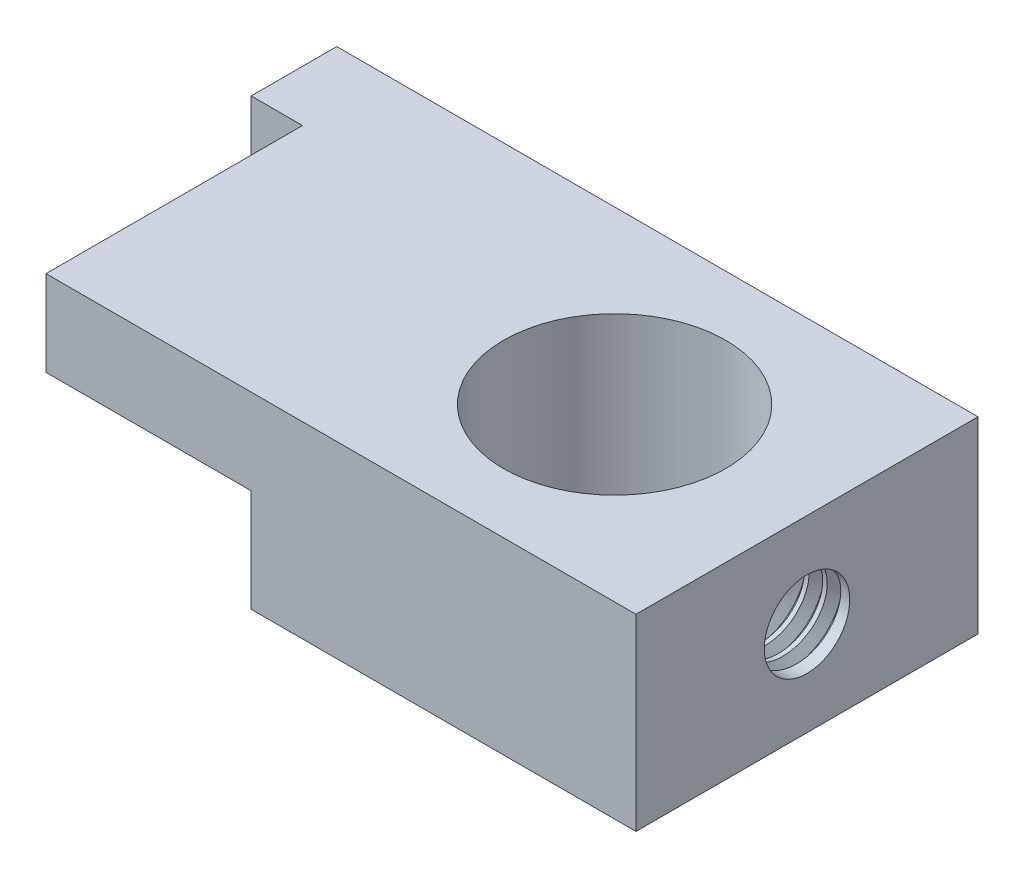
SolidWorks part; units mm, degrees
ref_plane "Front Plane" through (0, 0, 0) normal (0, 0, 1) x (1, 0, 0)
ref_plane "Top Plane" through (0, 0, 0) normal (0, 1, 0) x (1, 0, 0)
ref_plane "Right Plane" through (0, 0, 0) normal (1, 0, 0) x (0, 0, -1)
sketch "Sketch1" plane through (0, 0, 0) normal (0, 0, 1) x (1, 0, 0)
  line L1 (0, 0) -> (-22.5, 0)
  line L2 (0, 0) -> (0, -11)
  line L3 (0, -11) -> (-22.5, -11)
  line L4 (-22.5, 0) -> (-22.5, -11)
  dimension "D1" = 11
  dimension "D2" = 22.5
extrude "Boss-Extrude1" add sketch "Sketch1" along normal blind 20
sketch "Sketch3" plane through (0, 0, 0) normal (0, 1, 0) x (1, 0, 0)
  line L0 (0, -20) -> (-22.5, -20) construction
  line L1 (0, -20) -> (0, 0) construction
  circle A0 centre (-11.25, -10) radius 6.5
  point P4 (-11.25, -20)
  point P7 (0, -10)
  dimension "D1" = 0
  dimension "D2" = 0
  dimension "D3" = 13
extrude "Cut-Extrude1" cut sketch "Sketch3" against normal blind 26
sketch "Sketch4" plane through (0, 0, 0) normal (1, 0, 0) x (0, 0, -1)
  line L0 (-20, 0) -> (0, 0) construction
  line L1 (0, -11) -> (0, 0) construction
  circle A0 centre (-10, -5.5) radius 2.5
  point P4 (-10, 0)
  point P7 (0, -5.5)
  dimension "D1" = 0
  dimension "D2" = 0
  dimension "D3" = 5
extrude "Cut-Extrude2" cut sketch "Sketch4" against normal blind 9
sketch "Sketch6" plane through (-22.5, 0, 0) normal (-1, 0, 0) x (0, 0, 1)
  line L0 (20, 0) -> (0, 0) construction
  line L1 (0, -11) -> (5, -11)
  line L2 (0, -11) -> (0, 0)
  line L3 (0, 0) -> (5, 0)
  line L4 (5, -11) -> (5, 0)
  dimension "D1" = 5
extrude "Boss-Extrude4" add sketch "Sketch6" along normal blind 15
thread "Thread1" pitch 1.0583 method cut profile "Thread Profile1" start angle 0, offset 0, length 6, pitch 1.0583, diameter 5
ref_plane "Plane1" through (0, -5.5, 12.5) normal (0, -1, 0) x (0, 0, 1)
sketch "Thread Profile1" plane through (0, -5.5, 12.5) normal (0, -1, 0) x (0, 0, 1)
  line L0 (0, 0) -> (0, 1.0583) construction
  line L1 (0, 0) -> (0.5728, 0.3307)
  line L2 (0.5728, 0.3307) -> (0.5728, 0.463)
  line L3 (0.5728, 0.463) -> (0, 0.7937)
  line L4 (0.5728, 0.3969) -> (0, 0.3969) construction
  line L11 (0, 0) -> (0, 0.7937)
  point P2 (0, 0)
  dimension "Pitch" = 1.0583
  dimension "Profile_Angle" = 60
  dimension "Profile_Land" = 0.1323
  dimension "Profile_Height" = 0.5728
sketch "Sketch7" plane through (-22.5, 0, 0) normal (-1, 0, 0) x (0, 0, 1)
  line L0 (5, -11) -> (5, 0) construction
  line L1 (20, 0) -> (5, 0)
  line L2 (20, 0) -> (20, -5)
  line L3 (20, -5) -> (5, -5)
  line L4 (5, 0) -> (5, -5)
  dimension "D1" = 5
extrude "Boss-Extrude5" add sketch "Sketch7" along normal blind 12
